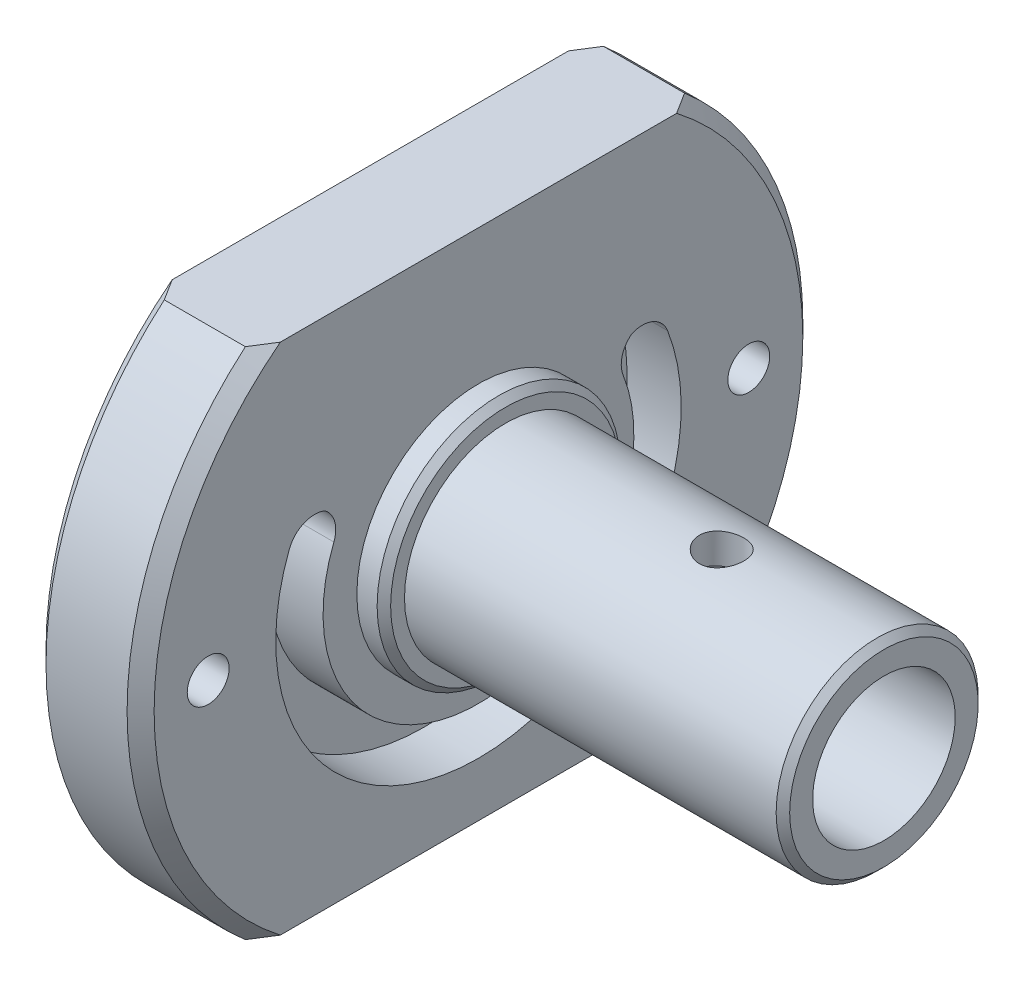
SolidWorks part; units mm, degrees
material "6061 Alloy"
ref_plane "前视基准面" through (0, 0, 0) normal (0, 0, 1) x (1, 0, 0)
ref_plane "上视基准面" through (0, 0, 0) normal (0, 1, 0) x (1, 0, 0)
ref_plane "右视基准面" through (0, 0, 0) normal (1, 0, 0) x (0, 0, -1)
sketch "草图1" plane through (0, 0, 0) normal (0, 1, 0) x (1, 0, 0)
  line L0 (-70.2175, 0) -> (139.68, 0) construction
  line L1 (38, 0) -> (38, 7.475)
  line L2 (38, 7.475) -> (10, 7.475)
  line L3 (10, 7.475) -> (10, 9)
  line L4 (10, 9) -> (8, 9)
  line L5 (8, 9) -> (8, 25)
  line L6 (8, 25) -> (0, 25)
  line L7 (0, 25) -> (0, 0)
  line L8 (0, 0) -> (38, 0)
  dimension "D1" = 7.475
  dimension "D2" = 28
  dimension "D3" = 9
  dimension "D4" = 2
  dimension "D5" = 8
  dimension "D6" = 25
revolve "旋转1" add sketch "草图1" angle 360 about L0
sketch "草图3" plane through (38, 0, 0) normal (1, 0, 0) x (0, 0, -1)
  circle A0 centre (0, 0) radius 5.275
  dimension "D1" = 10.55
extrude "切除-拉伸1" cut sketch "草图3" against normal blind 15
chamfer "倒角1" distance 0.5 angle 45 1 edges at (38, 0, 7.475)
ref_plane "基准面1" through (0, 7.5, 0) normal (0, 1, 0) x (1, 0, 0)
sketch "草图5" plane through (0, 7.5, 0) normal (0, 1, 0) x (1, 0, 0)
  point P0 (30.5, 0)
hole_wizard "M4 Tapped Hole1" positions "3D草图8" profile "草图10" tap size "M4" standard "GB"
sketch3d "3D草图8"
  point P0 (26, 7.475, 0)
  point P2 (30.5, 7.5, 0)
  point P5 (30.5, 7.5, 0)
  dimension "D1" = 3
sketch "草图10" plane through (26, 7.475, 0) normal (1, 0, 0) x (0, 0, 1)
  line L0 (0, 0) -> (0, 30.4914)
  line L1 (0, 30.4914) -> (1.65, 29.5)
  line L2 (1.65, 29.5) -> (1.65, 0)
  line L5 (1.65, 0) -> (0, 0)
  line L10 (0, 30.4914) -> (-1.65, 29.5) construction
  line L11 (0, -6.35) -> (0, 107.95) construction
  dimension "螺纹孔钻头直径" = 3.3
  dimension "螺纹孔钻头深度" = 29.5
  dimension "导头角度" = 118
cosmetic thread "Hole Thread1" parameters "D1"=14.95, "D2"=4
chamfer "倒角2" distance 1 angle 45 1 edges at (8, 0, 25)
chamfer "倒角3" distance 1 angle 45 1 edges at (0, 0, 25)
chamfer "倒角5" distance 0.5 angle 45 1 edges at (10, 0, 9)
sketch "草图14" plane through (8, 0, 0) normal (1, 0, 0) x (0, 0, -1)
  line L0 (0, 24.2394) -> (0, 10.25) construction
  line L1 (9.9593, 5.75) -> (12.9904, 7.5)
  line L3 (0, 0) -> (0, -27.6028) construction
  line L4 (-9.9593, 5.75) -> (-12.9904, 7.5)
  arc A0 (-9.9593, 5.75) -> (9.9593, 5.75) centre (0, 0) ccw
  arc A1 (-12.9904, 7.5) -> (12.9904, 7.5) centre (0, 0) ccw
  dimension "D1" = 23
  dimension "D2" = 30
  dimension "D4" = 60
extrude "切除-拉伸6" cut sketch "草图14" against normal blind 4
fillet "圆角3" radius 2 4 edges at (6, 7.5, -12.9904) (6, 5.75, -9.9593) (6, 5.75, 9.9593) (6, 7.5, 12.9904)
ref_plane "Plane1" through (0, 0, 0) normal (0, 0.7071, -0.7071) x (-1, 0, 0)
mirror "Mirror1" [suppressed] about plane through (0, 0, 0) normal (0, 0.7071, -0.7071)
sketch "Sketch1" plane through (0, 0, 0) normal (-1, 0, 0) x (0, 0, 1)
  line L0 (0, 0) -> (0, 50.7232) construction
  circle A1 centre (20, 0) radius 1.55
  circle A3 centre (-20, 0) radius 1.55
  point P14 (0, 0)
extrude "Cut-Extrude1" cut sketch "Sketch1" against normal through all
sketch "Sketch2" plane through (0, 0, 0) normal (-1, 0, 0) x (0, 0, 1)
  circle A0 centre (0, 0) radius 2.55
  dimension "D1" = 5.1
extrude "Cut-Extrude2" cut sketch "Sketch2" against normal through all
sketch "Sketch3" plane through (0, 0, 0) normal (-1, 0, 0) x (0, 0, 1)
  circle A0 centre (0, 0) radius 5
  dimension "D1" = 10
extrude "Cut-Extrude3" cut sketch "Sketch3" against normal blind 18
sketch "Sketch4" plane through (0, 0, 0) normal (-1, 0, 0) x (0, 0, 1)
  line L0 (0, 0) -> (55.1663, 0) construction
  line L1 (-29.0416, -19) -> (34.4854, -19)
  line L2 (-29.0416, 29.7791) -> (34.4854, 29.7791)
  line L3 (-29.0416, 29.7791) -> (-29.0416, 19)
  line L4 (-29.0416, 19) -> (34.4854, 19)
  line L5 (34.4854, 29.7791) -> (34.4854, 19)
  line L6 (34.4854, -29.7791) -> (34.4854, -19)
  line L7 (-29.0416, -29.7791) -> (34.4854, -29.7791)
  line L8 (-29.0416, -29.7791) -> (-29.0416, -19)
  dimension "D1" = 19
extrude "Cut-Extrude4" cut sketch "Sketch4" against normal blind 10
